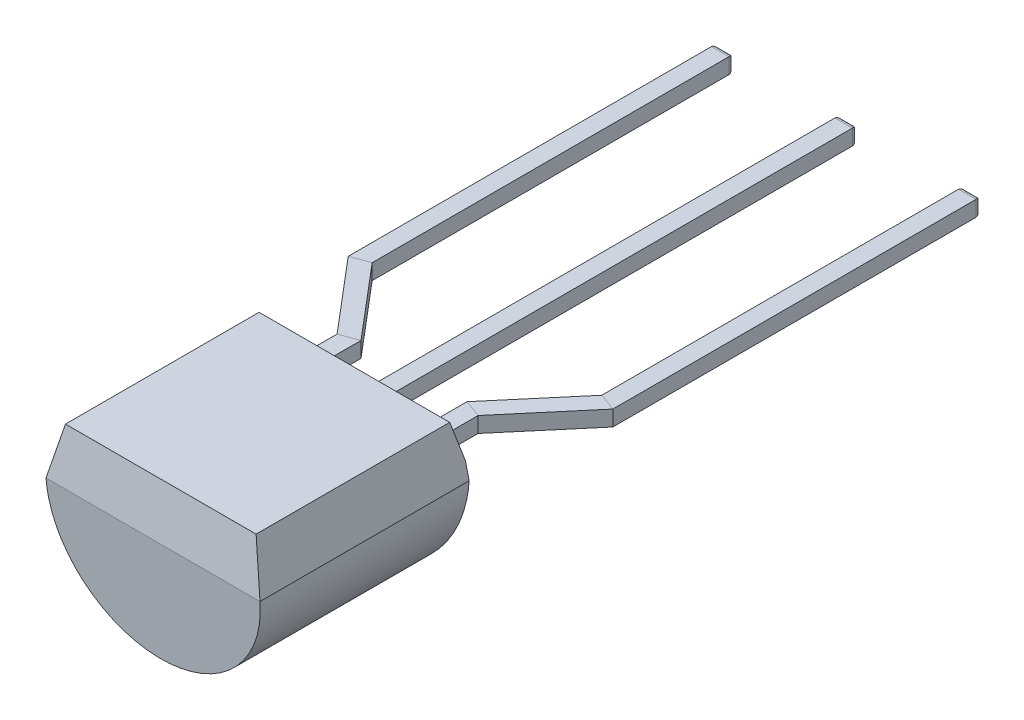
SolidWorks part; units mm, degrees
ref_plane "Front Plane" through (0, 0, 0) normal (0, 0, 1) x (1, 0, 0)
ref_plane "Top Plane" through (0, 0, 0) normal (0, 1, 0) x (1, 0, 0)
ref_plane "Right Plane" through (0, 0, 0) normal (1, 0, 0) x (0, 0, -1)
sketch "Sketch1" plane through (0, 0, 0) normal (0, 0, 1) x (1, 0, 0)
  line L0 (-1.9596, 1) -> (-2.2, 0)
  line L1 (-1.9596, 1) -> (1.9596, 1)
  line L3 (1.9596, 1) -> (2.2, 0)
  arc A0 (-2.2, 0) -> (2.2, 0) centre (0, 0) ccw
  dimension "D1" = 4.4
extrude "Boss-Extrude1" add sketch "Sketch1" along normal blind 4.3 contours L0 A0 L3 L1
sketch "Sketch2" plane through (0, 0, 0) normal (0, 0, 1) x (1, 0, 0)
  line L0 (-0.18, 0) -> (0.18, 0)
  line L1 (1.09, 0) -> (1.45, 0)
  line L2 (1.09, 0.32) -> (1.45, 0.32)
  line L3 (-0.18, 0.32) -> (0.18, 0.32)
  line L4 (-0.18, 0.32) -> (-0.18, 0)
  line L5 (-0.18, 0) -> (0.18, 0)
  line L6 (0.18, 0.32) -> (0.18, 0)
  line L7 (1.09, 0.32) -> (1.09, 0)
  line L8 (1.09, 0) -> (1.45, 0)
  line L9 (1.45, 0.32) -> (1.45, 0)
  line L10 (-1.45, 0) -> (-1.09, 0)
  line L11 (-1.45, 0.32) -> (-1.09, 0.32)
  line L12 (-1.45, 0.32) -> (-1.45, 0)
  line L13 (-1.45, 0) -> (-1.09, 0)
  line L14 (-1.09, 0.32) -> (-1.09, 0)
  point P1 (1.27, 0.16)
  point P7 (0, 0.16)
  point P14 (-1.27, 0.16)
  dimension "D1" = 2
  dimension "D2" = 0.36
  dimension "D3" = 2
sketch3d "3DSketch1" plane through (0, 0, 0) normal (0, 0, 1) x (1, 0, 0)
sketch3d "3DSketch2"
  line L0 (1.27, 0.16, 0) -> (1.27, 0.16, -1)
  line L3 (1.27, 0.16, 0) -> (1.27, 0.16, -1)
  line L7 (2.54, 0.16, -10) -> (2.54, 0.16, -2.5)
  line L8 (1.27, 0.16, -1) -> (2.54, 0.16, -2.5)
  dimension "D1" = 1
  dimension "D3" = 7.5
sweep "Sweep1" add profiles "Sketch2" path "3DSketch2"
mirror "Mirror1" about plane through (0, 0, 0) normal (1, 0, 0) of "Sweep1"
extrude "Boss-Extrude2" add sketch "Sketch2<4>" against normal blind 10 contours L6 L3 L4 L0 region at (0, 0.16, 0)
sketch "Sketch2<4>" plane through (0, 0, 0) normal (0, 0, 1) x (1, 0, 0) same geometry as "Sketch2"
fillet "Fillet1" radius 0.1 12 edges at (-2.54, 0.32, -10) (-2.72, 0.16, -10) (-2.54, 0, -10) (-2.36, 0.16, -10) (0, 0.32, -10) (-0.18, 0.16, -10) (0, 0, -10) (0.18, 0.16, -10) (2.36, 0.16, -10) (2.54, 0.32, -10) (2.72, 0.16, -10) (2.54, 0, -10)
ref_plane "Plane1" through (0, -2.2, 0) normal (0, 1, 0) x (1, 0, 0)
sketch "Sketch4" plane through (0, -2.2, 0) normal (0, 1, 0) x (1, 0, 0)
  circle A0 centre (0, -2.15) radius 0.8
  dimension "D1" = 1.6
extrude "Cut-Extrude1" cut sketch "Sketch4" along normal blind 0.25 contours A0 | A0 region at (0, -2.2, 2.15)
ref_plane "Plane3" through (2.2, 0, 0) normal (1, 0, 0) x (0, 0, -1)
sketch "Sketch5" plane through (2.2, 0, 0) normal (1, 0, 0) x (0, 0, -1)
  line L0 (-4.3, 0) -> (-4.14, 1)
  line L1 (-4.3, 0) -> (-4.14, 0)
  line L2 (-4.3, 0) -> (-4.3, 1)
  line L3 (-4.3, 1) -> (-4.14, 1)
  dimension "D1" = 0.16
  dimension "D2" = 1
extrude "Cut-Extrude2" cut sketch "Sketch5" against normal blind 5 contours L3 L2 L0 region at (2.2, 0.6667, 4.2467)
sketch "Sketch6" plane through (2.2, 0, 0) normal (1, 0, 0) x (0, 0, -1)
  line L0 (-4.3, 0) -> (-4.14, -2.2)
  line L2 (-4.3, 0) -> (-4.3, -2.2)
  line L3 (-4.3, -2.2) -> (-4.14, -2.2)
  dimension "D1" = 0.16
  dimension "D2" = 2.2
extrude "Cut-Extrude3" cut sketch "Sketch6" against normal blind 5
sketch "Sketch7" plane through (2.2, 0, 0) normal (1, 0, 0) x (0, 0, -1)
  line L0 (2.1556, -2.2) -> (-2.1556, -2.2) construction
  line L2 (0, 0) -> (0, -2.2)
  line L3 (0, -2.2) -> (-0.16, -2.2)
  line L5 (0, 0) -> (-0.16, -2.2)
  dimension "D1" = 0.16
extrude "Cut-Extrude4" cut sketch "Sketch7" against normal blind 5
sketch "Sketch8" plane through (2.2, 0, 0) normal (1, 0, 0) x (0, 0, -1)
  line L0 (-4.14, 1) -> (0, 1) construction
  line L2 (0, 0.32) -> (0, 1)
  line L3 (0, 1) -> (-0.16, 1)
  line L5 (-0.16, 1) -> (0, 0.32)
  dimension "D1" = 0.16
extrude "Cut-Extrude6" cut sketch "Sketch8" against normal blind 5 contours L2 L3 L5
sketch "Sketch9" plane through (0, -1.95, 0) normal (0, -1, 0) x (1, 0, 0)
extrude "Cut-Extrude8" cut sketch "Sketch4<3>" along normal blind 0.3
sketch "Sketch4<3>" plane through (0, -2.2, 0) normal (0, 1, 0) x (1, 0, 0) same geometry as "Sketch4"
